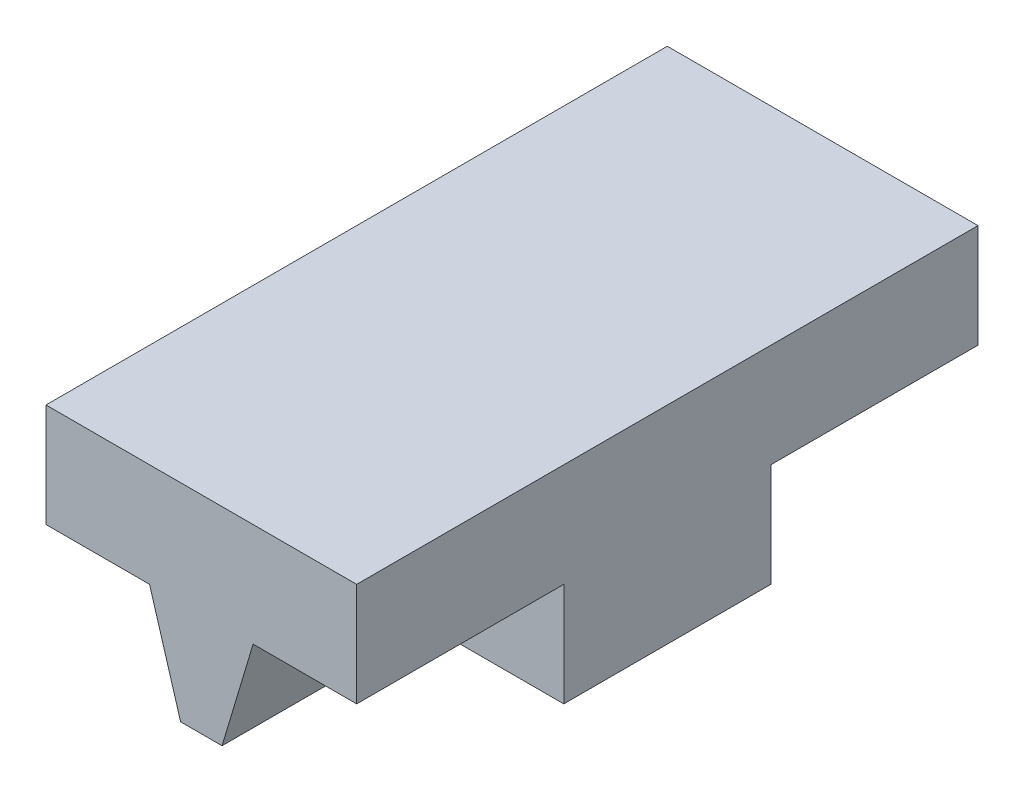
SolidWorks part; units mm, degrees
ref_plane "Front Plane" through (0, 0, 0) normal (0, 0, 1) x (1, 0, 0)
ref_plane "Top Plane" through (0, 0, 0) normal (0, 1, 0) x (1, 0, 0)
ref_plane "Right Plane" through (0, 0, 0) normal (1, 0, 0) x (0, 0, -1)
sketch "Sketch2" plane through (0, 0, 0) normal (1, 0, 0) x (0, 0, -1)
  line L1 (-300, 100) -> (300, 100)
  line L2 (-300, 100) -> (-300, -100)
  line L3 (-300, -100) -> (300, -100)
  line L4 (300, 100) -> (300, -100)
  line L5 (-300, 100) -> (300, -100) construction
  line L6 (-300, -100) -> (300, 100) construction
  point P0 (0, 0)
  dimension "D1" = 600
  dimension "D2" = 200
extrude "Boss-Extrude1" add sketch "Sketch2" along normal blind 150 and the other way blind 150
sketch "Sketch3" plane through (150, 0, 0) normal (1, 0, 0) x (0, 0, -1)
  line L1 (-300, -100) -> (-100, -100)
  line L2 (-300, -100) -> (-300, 0)
  line L3 (-300, 0) -> (-100, 0)
  line L4 (-100, -100) -> (-100, 0)
  line L5 (300, -100) -> (100, -100)
  line L6 (300, -100) -> (300, 0)
  line L7 (300, 0) -> (100, 0)
  line L8 (100, -100) -> (100, 0)
  dimension "D1" = 200
  dimension "D2" = 200
  dimension "D3" = 100
  dimension "D4" = 100
extrude "Cut-Extrude1" cut sketch "Sketch3" against normal blind 100
mirror "Mirror1" about plane through (0, 0, 0) normal (1, 0, 0) of "Cut-Extrude1"
sketch "Sketch4" plane through (0, 0, 0) normal (0, -1, 0) x (1, 0, 0)
  line L0 (50, 300) -> (150, 300) construction
  line L1 (100, 225) -> (125, 225)
  line L2 (100, 225) -> (100, 200)
  line L3 (100, 200) -> (125, 200)
  line L4 (125, 225) -> (125, 200)
  line L5 (150, 100) -> (150, 300) construction
  dimension "D1" = 25
  dimension "D2" = 25
  dimension "D3" = 75
  dimension "D4" = 25
extrude "Boss-Extrude2" add sketch "Sketch4" along normal blind 5
mirror "Mirror2" about plane through (0, 0, 0) normal (1, 0, 0) of "Boss-Extrude2"
mirror "Mirror3" about plane through (0, 0, 0) normal (0, 0, 1) of "Mirror2"
sketch "Sketch5" plane through (0, 0, -300) normal (0, 0, -1) x (-1, 0, 0)
  line L0 (-50, 0) -> (50, 0)
  line L1 (50, 0) -> (20, -100)
  line L2 (50, -100) -> (-50, -100) construction
  line L3 (20, -100) -> (-20, -100)
  line L4 (-20, -100) -> (-50, 0)
  line L5 (50, 0) -> (50, -100) construction
  line L6 (-50, 0) -> (-50, -100) construction
  line M1 (50, -100) -> (50, 0)
  line M7 (-50, 0) -> (-50, -100)
  line M8 (-50, -100) -> (50, -100)
  dimension "D1" = 30
  dimension "D2" = 30
extrude "Cut-Extrude3" cut sketch "Sketch5" against normal blind 200 contours L4 M8 M7 | L1 M1 M8 region at (40, -66.6667, -300) region at (-40, -66.6667, -300)
mirror "Mirror4" about plane through (0, 0, 0) normal (0, 0, 1) of "Cut-Extrude3"
